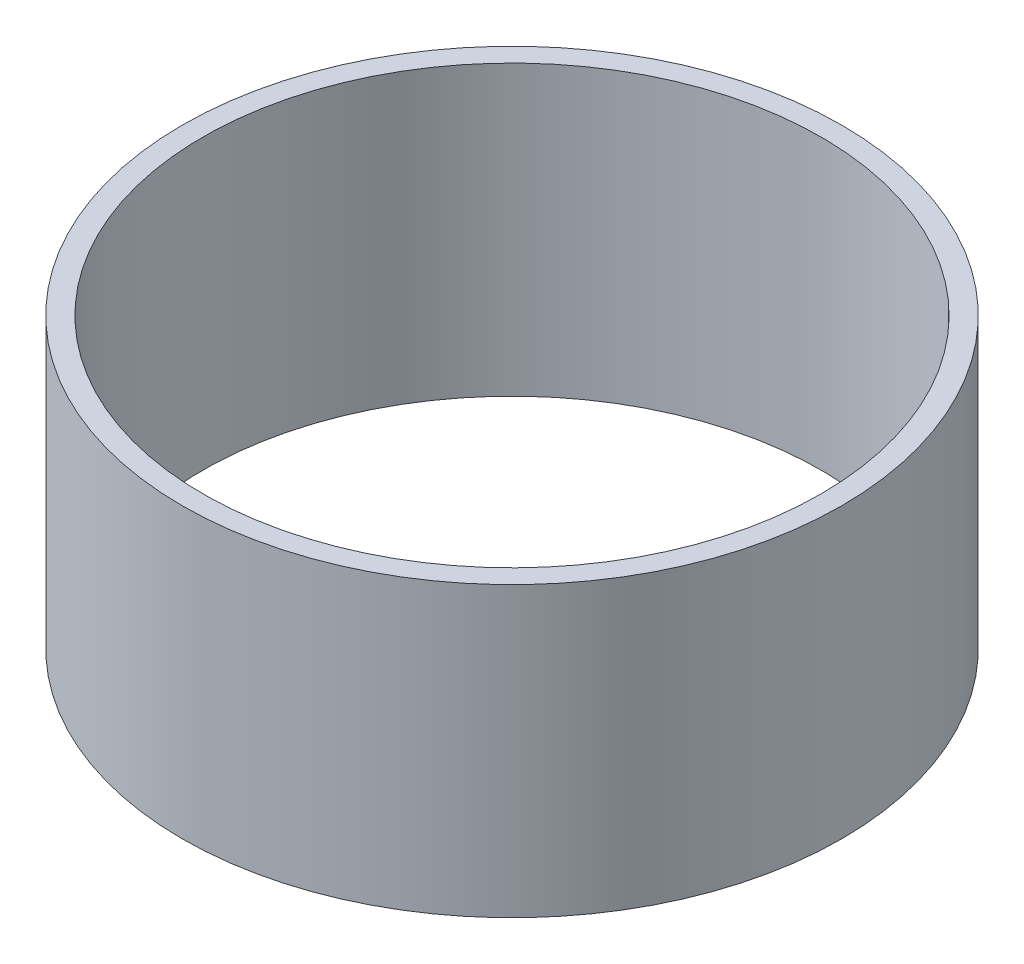
SolidWorks part; units mm, degrees
ref_plane "Спереди" through (0, 0, 0) normal (0, 0, 1) x (1, 0, 0)
ref_plane "Сверху" through (0, 0, 0) normal (0, 1, 0) x (1, 0, 0)
ref_plane "Справа" through (0, 0, 0) normal (1, 0, 0) x (0, 0, -1)
sketch "Эскиз1" plane through (0, 0, 0) normal (0, 1, 0) x (1, 0, 0)
  circle A0 centre (0, 0) radius 80
extrude "Вытянуть-Тонкостенный1" add sketch "Эскиз1" along normal blind 70 thin thin type one direction reverse wall 5
